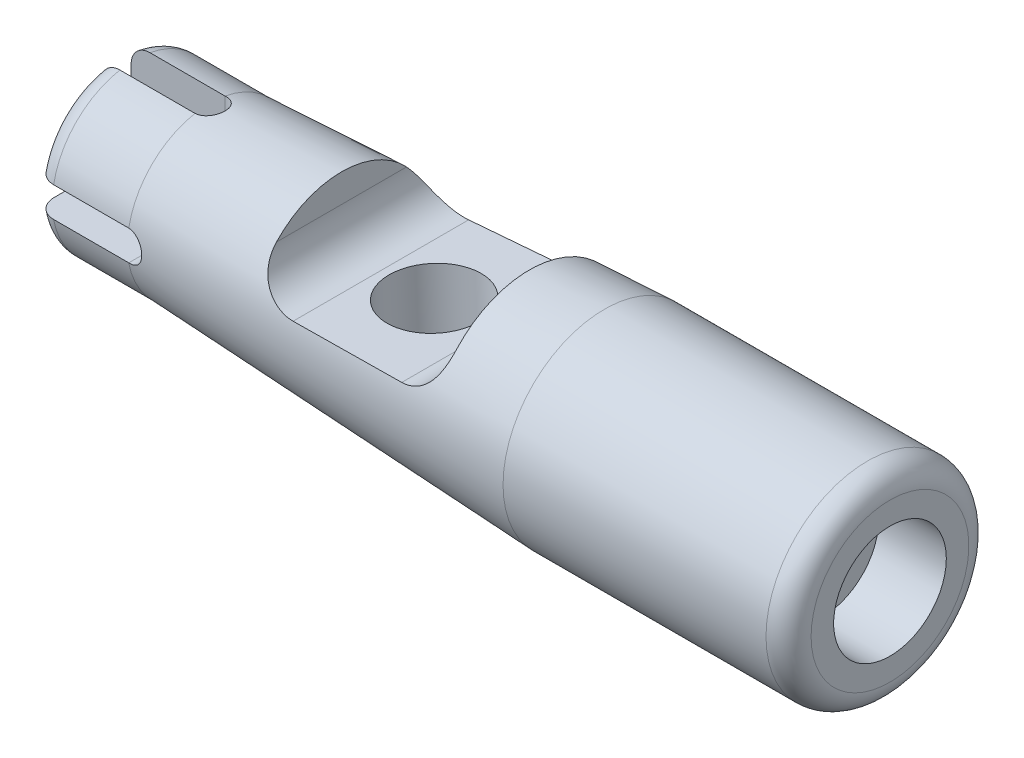
SolidWorks part; units mm, degrees
ref_plane "Front Plane" through (0, 0, 0) normal (0, 0, 1) x (1, 0, 0)
ref_plane "Top Plane" through (0, 0, 0) normal (0, 1, 0) x (1, 0, 0)
ref_plane "Right Plane" through (0, 0, 0) normal (1, 0, 0) x (0, 0, -1)
sketch "Sketch1" plane through (0, 0, 0) normal (0, 0, 1) x (1, 0, 0)
  line L0 (-109.5775, 0) -> (96.4225, 0) construction
  line L1 (90.4225, 27) -> (20.4225, 27)
  line L2 (20.4225, 27) -> (-84.5775, 22)
  line L3 (-84.5775, 22) -> (-104.5775, 22)
  line L4 (-109.5775, 17) -> (-109.5775, 0)
  line L5 (-109.5775, 0) -> (96.4225, 0)
  line L6 (96.4225, 0) -> (96.4225, 21)
  arc A0 (-104.5775, 22) -> (-109.5775, 17) centre (-104.5775, 17) ccw
  arc A1 (90.4225, 27) -> (96.4225, 21) centre (90.4225, 21) cw
  point P9 (-109.5775, 22)
  point P12 (96.4225, 27)
  dimension "D4" = 5
  dimension "D7" = 6
  dimension "D1" = 25
  dimension "D2" = 105
  dimension "D3" = 76
  dimension "D5" = 22
  dimension "D6" = 27
revolve "Revolve1" add sketch "Sketch1" angle 360 about L0
sketch "Sketch2" plane through (0, 0, 0) normal (0, 0, 1) x (1, 0, 0)
  line L0 (-123.827, 0) -> (-84.5775, 0) construction
  line L1 (-123.827, 4) -> (-84.5775, 4)
  line L2 (-123.827, -4) -> (-84.5775, -4)
  line L3 (20.4225, 27) -> (20.4225, -27) construction
  arc A0 (-123.827, 4) -> (-123.827, -4) centre (-123.827, 0) ccw
  arc A1 (-84.5775, -4) -> (-84.5775, 4) centre (-84.5775, 0) ccw
  point P3 (-104.2022, 0)
  dimension "D1" = 4
  dimension "D2" = 105
extrude "Cut-Extrude1" cut sketch "Sketch2" against normal through all both and the other way through all
sketch "Sketch3" plane through (0, 0, 0) normal (0, 0, 1) x (1, 0, 0)
  line L0 (0.4225, 26.0476) -> (0.4225, 17.5624)
  line L1 (-9.1018, 7.5737) -> (-39.1018, 6.1451)
  line L2 (-49.5775, 16.1338) -> (-49.5775, 23.6667)
  line L3 (20.4225, 27) -> (-84.5775, 22) construction
  line L4 (-49.5775, 23.6667) -> (0.4225, 26.0476)
  line L5 (20.4225, 27) -> (20.4225, -27) construction
  arc A0 (0.4225, 17.5624) -> (-9.1018, 7.5737) centre (-9.5775, 17.5624) cw
  arc A1 (-39.1018, 6.1451) -> (-49.5775, 16.1338) centre (-39.5775, 16.1338) cw
  point P7 (-8.6092, 25.5546)
  point P13 (0.4225, 26.0476)
  dimension "D4" = 10
  dimension "D5" = 10
  dimension "D1" = 18
  dimension "D2" = 50
  dimension "D3" = 20
extrude "Cut-Extrude2" cut sketch "Sketch3" against normal through all both and the other way through all
sketch "Sketch4" plane through (0, 0, 0) normal (0, 0, 1) x (1, 0, 0)
  line L0 (20.4225, -22) -> (77.5646, -22)
  line L2 (20.4225, -27) -> (90.4225, -27) construction
  line L5 (20.4225, -27) -> (77.5646, -27)
  line L6 (77.5646, -22) -> (77.5646, -27)
  line L7 (20.4225, -22) -> (20.4225, -27)
  dimension "D3" = 5
extrude "Cut-Extrude3" cut sketch "Sketch4" against normal through all both and the other way through all contours L5 L6 L0 L7
sketch "Sketch5" plane through (0, -22, 0) normal (0, -1, 0) x (1, 0, 0)
  line L0 (25.4813, 0) -> (70.7144, 0) construction
  circle A0 centre (45.128, 12) radius 3
  circle A1 centre (45.128, -12) radius 3
  dimension "D1" = 6
  dimension "D2" = 6
  dimension "D3" = 12
  dimension "D4" = 12
extrude "Cut-Extrude4" cut sketch "Sketch5" against normal blind 12
sketch "Sketch6" plane through (96.4225, 0, 0) normal (1, 0, 0) x (0, 0, -1)
  circle A0 centre (0, 0) radius 15
  circle A1 centre (0, 0) radius 7.5
  dimension "D1" = 30
  dimension "D2" = 15
extrude "Cut-Extrude5" cut sketch "Sketch6" against normal blind 18 contours A0
extrude "Cut-Extrude6" cut sketch "Sketch6<3>" against normal blind 38 contours A1 region at (96.4225, 0, 0)
sketch "Sketch6<3>" plane through (96.4225, 0, 0) normal (1, 0, 0) x (0, 0, -1) same geometry as "Sketch6"
sketch "Sketch7" plane through (-0.3804, 7.989, 0) normal (-0.0476, 0.9989, 0) x (0.9989, 0.0476, 0)
  circle A0 centre (-24.5779, 0) radius 12
  ellipse E0 centre (0.4221, 0) end of major axis (0.4221, -26.0476) minor radius 1.239 (1.2574, -19.2365) -> (1.2574, 19.2365) ccw construction
  point P10 (0, 0)
  dimension "D1" = 24
  dimension "D2" = 25
extrude "Cut-Extrude7" cut sketch "Sketch7" against normal blind 16
pattern_circular "CirPattern1" count 4 over 360 about axis through (-109.5775, 0, 0) along (-1, 0, 0) of "Cut-Extrude1" reverse direction yes
fillet "Fillet2" radius 5 2 edges at (20.4225, -22, 0) (77.5646, -22, 0)
